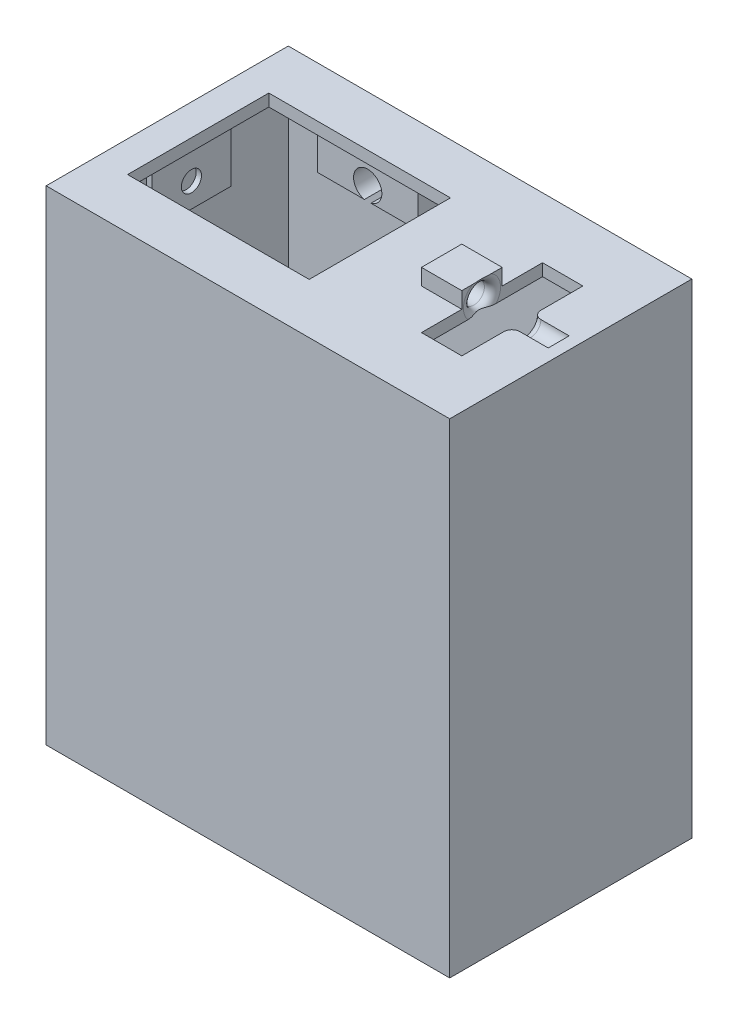
SolidWorks part; units mm, degrees
ref_plane "Front Plane" through (0, 0, 0) normal (0, 0, 1) x (1, 0, 0)
ref_plane "Top Plane" through (0, 0, 0) normal (0, 1, 0) x (1, 0, 0)
ref_plane "Right Plane" through (0, 0, 0) normal (1, 0, 0) x (0, 0, -1)
sketch "Sketch1" plane through (0, 0, 0) normal (0, 1, 0) x (1, 0, 0)
  line L1 (-63.5, -38.1) -> (63.5, -38.1)
  line L2 (-63.5, -38.1) -> (-63.5, 38.1)
  line L3 (-63.5, 38.1) -> (63.5, 38.1)
  line L4 (63.5, -38.1) -> (63.5, 38.1)
  line L5 (-63.5, -38.1) -> (63.5, 38.1) construction
  line L6 (-63.5, 38.1) -> (63.5, -38.1) construction
  point P0 (0, 0)
  dimension "D1" = 127
  dimension "D2" = 76.2
extrude "main body" add sketch "Sketch1" along normal blind 152.4
shell "hollow it" thickness 3.81 removed face at (0, 0, 0)
sketch "Sketch2" plane through (0, 152.4, 0) normal (0, 1, 0) x (1, 0, 0)
  line L0 (63.5, -38.1) -> (63.5, 38.1) construction
  line L1 (48.26, 19.05) -> (35.56, 19.05)
  line L2 (48.26, 19.05) -> (48.26, -19.05)
  line L3 (48.26, -19.05) -> (35.56, -19.05)
  line L4 (35.56, 19.05) -> (35.56, -19.05)
  line L5 (48.26, 19.05) -> (35.56, -19.05) construction
  line L6 (48.26, -19.05) -> (35.56, 19.05) construction
  point P0 (41.91, 0)
  dimension "D1" = 38.1
  dimension "D2" = 12.7
  dimension "D3" = 15.24
extrude "hole for scrollwheel" cut sketch "Sketch2" against normal up to next
ref_plane "arm guys plane" through (35.56, 0, 0) normal (1, 0, 0) x (0, 0, -1)
sketch "Sketch3" plane through (35.56, 0, 0) normal (1, 0, 0) x (0, 0, -1)
  line L0 (0, 152.4) -> (6.35, 152.4)
  line L1 (19.05, 152.4) -> (-19.05, 152.4) construction
  line L2 (6.35, 152.4) -> (6.35, 157.48)
  line L3 (6.35, 157.48) -> (-6.35, 157.48)
  line L4 (-6.35, 157.48) -> (-6.35, 152.4)
  line L5 (-6.35, 152.4) -> (0, 152.4)
  dimension "D1" = 6.35
  dimension "D2" = 6.35
  dimension "D3" = 5.08
extrude "nibble base hole" add sketch "Sketch3" against normal blind 12.7
ref_point "nibble base point"
sketch "Sketch5" plane through (35.56, 0, 0) normal (1, 0, 0) x (0, 0, -1)
  circle A0 centre (0, 152.4) radius 3.302
extrude "nibble hole" cut sketch "Sketch5" against normal blind 11.43 and the other way blind 24.13
fillet "easy to insert scroll wheel" radius 2.54 2 edges at (48.26, 149.098, 0) (35.56, 152.4, 3.302)
sketch "Sketch6" plane through (0, 152.4, 0) normal (0, 1, 0) x (1, 0, 0)
  line L1 (3.4013, 22.225) -> (-53.7487, 22.225)
  line L2 (3.4013, 22.225) -> (3.4013, -22.225)
  line L3 (3.4013, -22.225) -> (-53.7487, -22.225)
  line L4 (-53.7487, 22.225) -> (-53.7487, -22.225)
  line L5 (3.4013, 22.225) -> (-53.7487, -22.225) construction
  line L6 (3.4013, -22.225) -> (-53.7487, 22.225) construction
  point P0 (-25.1737, 0)
  dimension "D1" = 57.15
  dimension "D2" = 44.45
  dimension "D3" = 0
extrude "hole for joystick" cut sketch "Sketch6" against normal blind 11.43
sketch "Sketch10" plane through (0, 148.59, 0) normal (0, -1, 0) x (1, 0, 0)
  line L0 (-59.69, 34.29) -> (59.69, 34.29) construction
  line L1 (-47.3987, 31.75) -> (-2.9487, 31.75)
  line L2 (-47.3987, 31.75) -> (-47.3987, 24.765)
  line L3 (-47.3987, 24.765) -> (-2.9487, 24.765)
  line L4 (-2.9487, 31.75) -> (-2.9487, 24.765)
  line L5 (-47.3987, 31.75) -> (-2.9487, 24.765) construction
  line L6 (-47.3987, 24.765) -> (-2.9487, 31.75) construction
  line L7 (59.69, -34.29) -> (-59.69, -34.29) construction
  line L8 (-41.0487, -31.75) -> (-9.2987, -31.75)
  line L9 (-41.0487, -31.75) -> (-41.0487, -24.765)
  line L10 (-41.0487, -24.765) -> (-9.2987, -24.765)
  line L11 (-9.2987, -31.75) -> (-9.2987, -24.765)
  line L12 (-41.0487, -31.75) -> (-9.2987, -24.765) construction
  line L13 (-41.0487, -24.765) -> (-9.2987, -31.75) construction
  point P0 (-25.1737, 28.2575)
  point P5 (0, 34.29)
  point P10 (-25.1737, -28.2575)
  point P15 (0, -34.29)
  dimension "D1" = 6.35
  dimension "D2" = 6.35
  dimension "D3" = 2.54
  dimension "D4" = 2.54
  dimension "D5" = 2.54
  dimension "D6" = 2.54
extrude "box nibble base" add sketch "Sketch10" along normal blind 12.7
sketch "Sketch11" plane through (0, 148.59, 0) normal (0, -1, 0) x (1, 0, 0)
  line L0 (3.4013, -22.225) -> (3.4013, 22.225) construction
  line L1 (7.2113, -12.4282) -> (11.7833, -12.4282)
  line L2 (7.2113, -12.4282) -> (7.2113, 12.4282)
  line L3 (7.2113, 12.4282) -> (11.7833, 12.4282)
  line L4 (11.7833, -12.4282) -> (11.7833, 12.4282)
  line L5 (7.2113, -12.4282) -> (11.7833, 12.4282) construction
  line L6 (7.2113, 12.4282) -> (11.7833, -12.4282) construction
  line L7 (-53.7487, -22.225) -> (-53.7487, 22.225) construction
  line L8 (-55.88, -12.4282) -> (-57.5587, -12.4282)
  line L9 (-55.88, -12.4282) -> (-55.88, 12.4282)
  line L10 (-55.88, 12.4282) -> (-57.5587, 12.4282)
  line L11 (-57.5587, -12.4282) -> (-57.5587, 12.4282)
  line L12 (-55.88, -12.4282) -> (-57.5587, 12.4282) construction
  line L13 (-55.88, 12.4282) -> (-57.5587, -12.4282) construction
  line L14 (-59.69, -34.29) -> (-59.69, 34.29) construction
  point P0 (9.4973, 0)
  point P5 (3.4013, 0)
  point P8 (-56.7193, 0)
  point P14 (-53.7487, 0)
  point P17 (-59.69, 0)
  dimension "D1" = 3.81
  dimension "D2" = 4.572
  dimension "D3" = 3.81
  dimension "D4" = 3.81
  dimension "D5" = 1.6787
extrude "arch nibble base" add sketch "Sketch11" along normal blind 17.78
sketch "Sketch12" plane through (7.2113, 0, 0) normal (-1, 0, 0) x (0, 0, 1)
  line L1 (-22.225, 148.59) -> (22.225, 148.59) construction
  circle A0 centre (0, 138.43) radius 3.175
  dimension "D2" = 6.35
  dimension "D1" = 10.16
extrude "arch nibble holes" cut sketch "Sketch12" against normal up to surface and the other way up to surface up to face at (11.7833, 139.7, 0) other way up to face at (-59.69, 74.295, 0)
sketch "Sketch13" plane through (0, 0, -24.765) normal (0, 0, 1) x (1, 0, 0)
  line L0 (-9.2987, 135.89) -> (-9.2987, 148.59) construction
  line L1 (-41.0487, 135.89) -> (-41.0487, 148.59) construction
  circle A0 centre (-25.1737, 140.2129) radius 4.445
  point P2 (-9.2987, 142.24)
  point P5 (-41.0487, 142.24)
  dimension "D3" = 8.89
  dimension "D1" = 15.875
  dimension "D2" = 15.875
extrude "box nibble holes" cut sketch "Sketch13" against normal up to surface and the other way up to surface up to face at (0, 74.295, -34.29) other way up to face at (0, 74.295, 34.29)
